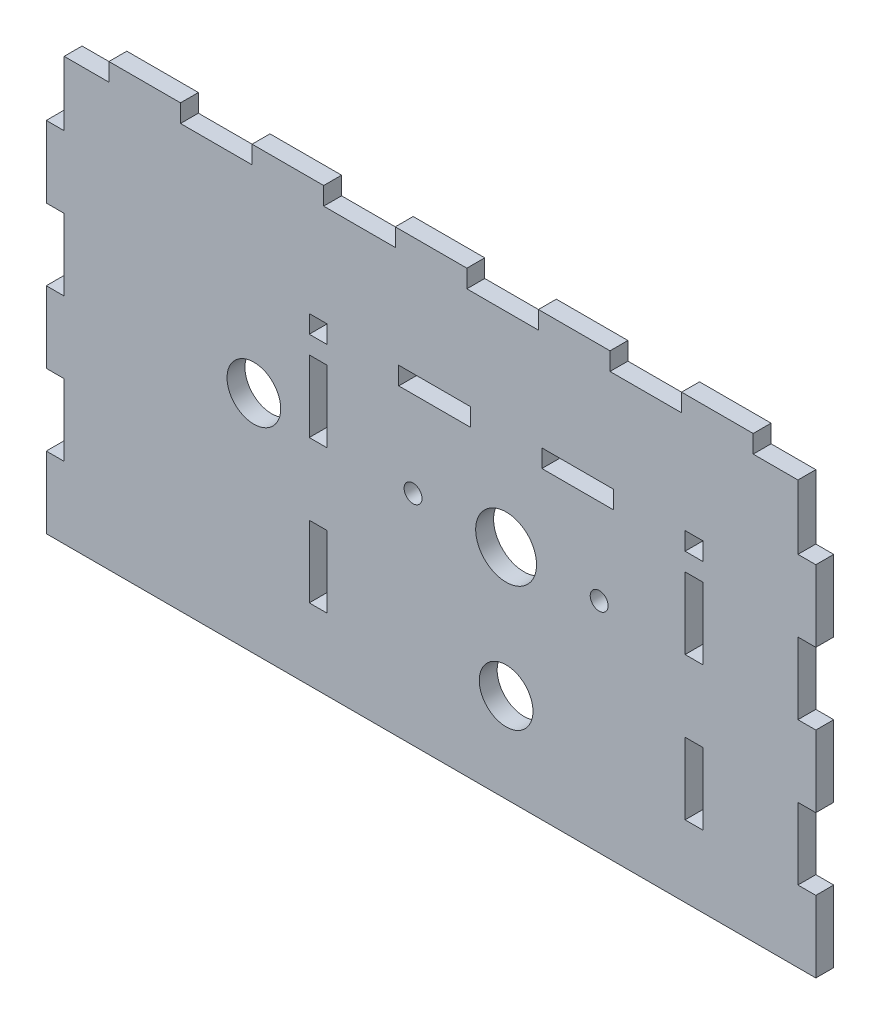
SolidWorks part; units mm, degrees
ref_plane "정면" through (0, 0, 0) normal (0, 0, 1) x (1, 0, 0)
ref_plane "윗면" through (0, 0, 0) normal (0, 1, 0) x (1, 0, 0)
ref_plane "우측면" through (0, 0, 0) normal (1, 0, 0) x (0, 0, -1)
sketch "스케치1" plane through (0, 0, 0) normal (0, 0, 1) x (1, 0, 0)
  line L0 (20.9716, 62.0818) -> (20.9716, -70.5321) construction
  line L1 (-102.5, 59) -> (102.5, 59)
  line L2 (-102.5, 59) -> (-102.5, -59)
  line L3 (-102.5, -59) -> (102.5, -59)
  line L4 (102.5, 59) -> (102.5, -59)
  line L5 (-102.5, 59) -> (102.5, -59) construction
  line L6 (-102.5, -59) -> (102.5, 59) construction
  line L7 (0, 66.5433) -> (0, -75.192) construction
  circle A0 centre (20.9716, 2) radius 8.5
  circle A1 centre (-49.5, 4) radius 7.5
  circle A5 centre (-5.0284, 2) radius 2.5
  circle A7 centre (46.9716, 2) radius 2.5
  circle A10 centre (20.9716, -34) radius 7.5
  point P0 (0, 0)
  dimension "D3" = 15
  dimension "D8" = 5
  dimension "D9" = 52
  dimension "D10" = 17
  dimension "D11" = 25
  dimension "D12" = 15
  dimension "D1" = 205
  dimension "D2" = 118
  dimension "D4" = 49.5
  dimension "D5" = 55
  dimension "D6" = 70.5
  dimension "D7" = 57
extrude "보스-돌출1" add sketch "스케치1" along normal blind 5 contours L4 L1 L2 L3 A0 A1 A5 A7 region at (-0.023, 0.2023, 0)
sketch "스케치2" plane through (0, 0, 5) normal (0, 0, 1) x (1, 0, 0)
  line L5 (102.5, -59) -> (107.5, -59)
  line L6 (102.5, -59) -> (102.5, -39)
  line L7 (102.5, -39) -> (107.5, -39)
  line L8 (107.5, -59) -> (107.5, -39)
  dimension "D1" = 5
  dimension "D2" = 20
extrude "보스-돌출2" add sketch "스케치2" against normal up to surface (5 mm away) contours L7 L8 L5 L6 up to face at (28.4716, -34, 0)
pattern_linear "선형 패턴2" count 3 spacing 40 along (0, 1, 0) of "보스-돌출2"
mirror "대칭 복사2" about plane through (0, 0, 0) normal (1, 0, 0) of "선형 패턴2"
sketch "스케치3" plane through (0, 0, 5) normal (0, 0, 1) x (1, 0, 0)
  line L0 (-102.5, 59) -> (102.5, 59) construction
  line L1 (10, 59) -> (-10, 59)
  line L2 (10, 59) -> (10, 64)
  line L3 (10, 64) -> (-10, 64)
  line L4 (-10, 59) -> (-10, 64)
  line L5 (0, 199.5713) -> (0, -71.5713) construction
  point P9 (0, 64)
  dimension "D1" = 5
  dimension "D2" = 20
extrude "보스-돌출3" add sketch "스케치3" against normal up to surface (5 mm away) up to face at (28.4716, -34, 0)
pattern_linear "선형 패턴3" count 3 spacing 40 along (1, 0, 0) of "보스-돌출3"
pattern_linear "선형 패턴4" count 3 spacing 40 along (-1, 0, 0) of "보스-돌출3"
sketch "스케치5" plane through (0, 0, 5) normal (0, 0, 1) x (1, 0, 0)
  line L0 (-107.5, -59) -> (107.5, -59) construction
  line L1 (70.9716, -59) -> (-29.0284, -59)
  line L2 (70.9716, -59) -> (70.9716, 26)
  line L3 (70.9716, 26) -> (-29.0284, 26)
  line L4 (-29.0284, -59) -> (-29.0284, 26)
  line L5 (20.9716, -34) -> (20.9716, -67.8623) construction
  line L6 (-29.0284, -39) -> (-34.0284, -39)
  line L7 (70.9716, -39) -> (75.9716, -39)
  line L8 (70.9716, -39) -> (70.9716, -19)
  line L9 (70.9716, -19) -> (75.9716, -19)
  line L10 (75.9716, -39) -> (75.9716, -19)
  line L15 (30.9716, 26) -> (50.9716, 26)
  line L16 (30.9716, 26) -> (30.9716, 31)
  line L17 (30.9716, 31) -> (50.9716, 31)
  line L18 (50.9716, 26) -> (50.9716, 31)
  line L19 (-34.0284, -39) -> (-34.0284, -19)
  line L20 (-29.0284, -19) -> (-34.0284, -19)
  line L21 (-29.0284, -19) -> (-29.0284, -39)
  dimension "D1" = 100
  dimension "D2" = 85
  dimension "D3" = 5
  dimension "D4" = 20
  dimension "D5" = 20
  dimension "D6" = 10
  dimension "D7" = 20
  dimension "D8" = 5
extrude "컷-돌출1" cut sketch "스케치5" against normal blind 5 contours L7 L10 L9 L2 | L19 L20 L21 L6 region at (73.4716, -29, 5)
pattern_linear "선형 패턴5" count 2 spacing 40 along (0, 1, 0) of "컷-돌출1"
extrude "컷-돌출2" cut sketch "스케치5<3>" against normal blind 5 contours L17 L18 L15 L16
sketch "스케치5<3>" plane through (0, 0, 5) normal (0, 0, 1) x (1, 0, 0) same geometry as "스케치5"
pattern_linear "선형 패턴6" count 2 spacing 40 along (-1, 0, 0) of "컷-돌출2"
sketch "스케치6" plane through (0, 0, 5) normal (0, 0, 1) x (1, 0, 0)
  line L0 (70.9716, 21) -> (75.9716, 21) construction
  line L1 (70.9716, 26) -> (75.9716, 26)
  line L2 (70.9716, 26) -> (70.9716, 31)
  line L3 (70.9716, 31) -> (75.9716, 31)
  line L4 (75.9716, 26) -> (75.9716, 31)
  line L5 (70.9716, 1) -> (70.9716, 21) construction
  line L6 (20.9716, 2) -> (20.9716, 42.4696) construction
  line L7 (-34.0284, 26) -> (-34.0284, 31)
  line L8 (-29.0284, 31) -> (-34.0284, 31)
  line L9 (-29.0284, 26) -> (-29.0284, 31)
  line L10 (-29.0284, 26) -> (-34.0284, 26)
  dimension "D1" = 5
  dimension "D2" = 5
  dimension "D3" = 5
extrude "컷-돌출3" cut sketch "스케치6" against normal blind 5
